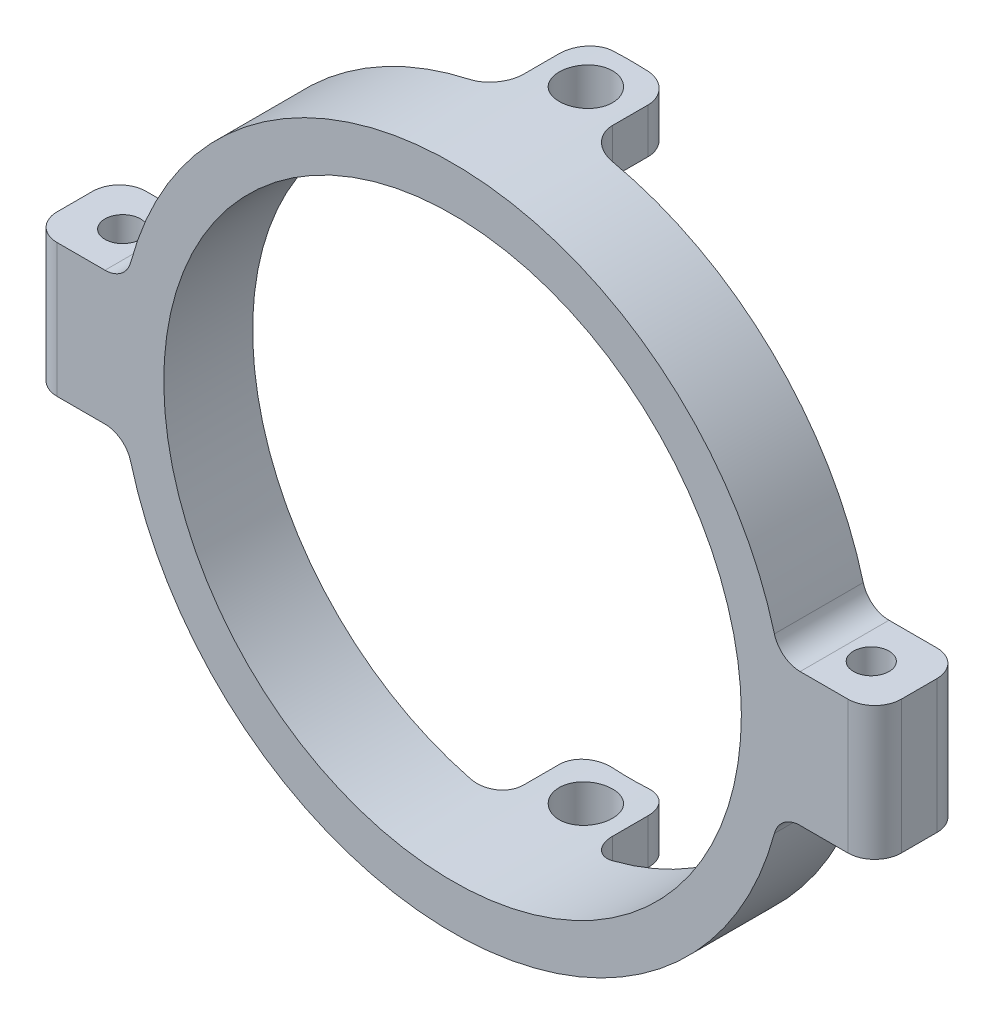
SolidWorks part; units mm, degrees
ref_plane "Alzado" through (0, 0, 0) normal (0, 0, 1) x (1, 0, 0)
ref_plane "Planta" through (0, 0, 0) normal (0, 1, 0) x (1, 0, 0)
ref_plane "Vista lateral" through (0, 0, 0) normal (1, 0, 0) x (0, 0, -1)
sketch "Croquis1" plane through (0, 0, 0) normal (0, 0, 1) x (1, 0, 0)
  circle A0 centre (0, 0) radius 32.5
  circle A1 centre (0, 0) radius 37.5
  dimension "D1" = 65
  dimension "D2" = 5
extrude "Saliente-Extruir1" add sketch "Croquis1" along normal blind 10
sketch "Croquis2" plane through (0, 0, 10) normal (0, 0, 1) x (1, 0, 0)
  line L0 (47.5, 7.5) -> (47.5, -7.5)
  line L1 (47.5, -7.5) -> (36.7423, -7.5)
  line L2 (36.7423, 7.5) -> (47.5, 7.5)
  line L3 (0, 10.498) -> (0, -9.1129) construction
  line L4 (-36.7423, 7.5) -> (-47.5, 7.5)
  line L5 (-47.5, 7.5) -> (-47.5, -7.5)
  line L6 (-47.5, -7.5) -> (-36.7423, -7.5)
  circle A0 centre (0, 0) radius 37.5 construction
  arc A2 (36.7423, 7.5) -> (36.7423, -7.5) centre (0, 0) cw
  arc A3 (-36.7423, 7.5) -> (-36.7423, -7.5) centre (0, 0) ccw
  point P7 (37.5, 0)
  point P8 (47.5, 0)
  dimension "D1" = 10
  dimension "D2" = 15
extrude "Saliente-Extruir2" add sketch "Croquis2" against normal blind 10
ref_plane "Plano1" through (0, 0, 0) normal (1, 0, 0) x (0, 0, -1)
sketch "Croquis3" plane through (0, -7.5, 0) normal (0, -1, 0) x (1, 0, 0)
  line L0 (47.5, 0) -> (47.5, 10) construction
  line L1 (36.7423, 0) -> (47.5, 0) construction
  line L2 (0, -5.5) -> (0, 5.5) construction
  circle A0 centre (42.1212, 5) radius 2
  circle A1 centre (-42.1212, 5) radius 2
  dimension "D1" = 4
  dimension "D2" = 5.3788
  dimension "D3" = 5
extrude "Cortar-Extruir1" cut sketch "Croquis3" against normal through all
sketch "Croquis4" plane through (0, 0, 0) normal (0, 0, -1) x (-1, 0, 0)
  line L0 (-5, -32.1131) -> (-5, -37.1652)
  line L1 (5, -32.1131) -> (5, -37.1652)
  line L2 (0, 0) -> (15.6938, 0) construction
  line L3 (-5, 32.1131) -> (-5, 37.1652)
  line L4 (5, 32.1131) -> (5, 37.1652)
  circle A0 centre (0, 0) radius 32.5 construction
  arc A1 (-5, -32.1131) -> (5, -32.1131) centre (0, 0) ccw
  arc A2 (-36.7423, -7.5) -> (36.7423, -7.5) centre (0, 0) ccw construction
  arc A3 (-5, -37.1652) -> (5, -37.1652) centre (0, 0) ccw
  arc A4 (-5, 32.1131) -> (5, 32.1131) centre (0, 0) cw
  arc A5 (-5, 37.1652) -> (5, 37.1652) centre (0, 0) cw
  point P6 (0, -32.5)
  dimension "D1" = 10
extrude "Saliente-Extruir3" add sketch "Croquis4" along normal blind 10
ref_plane "Plano2" through (0, -37.5, 0) normal (0, -1, 0) x (-1, 0, 0)
sketch "Croquis5" plane through (0, -37.5, 0) normal (0, -1, 0) x (-1, 0, 0)
  line L0 (-5, 10) -> (-5, 0) construction
  line L2 (5, 10) -> (-5, 10) construction
  circle A0 centre (0, 5) radius 3
  dimension "D1" = 6
  dimension "D2" = 5
  dimension "D3" = 5
extrude "Cortar-Extruir2" cut sketch "Croquis5" against normal through all
fillet "Redondeo2" radius 3 16 edges at (36.7423, 7.5, 5) (36.7423, -7.5, 5) (-5, 34.6391, -10) (5, 34.6391, -10) (5, 34.6391, 0) (47.5, 0, 10) (47.5, 0, 0) (-36.7423, 7.5, 5) (5, -34.6391, 0) (-5, -34.6391, -10) (5, -34.6391, -10) (-47.5, 0, 10) (-47.5, 0, 0) (-36.7423, -7.5, 5) (-5, 34.6391, 0) (-5, -34.6391, 0)
